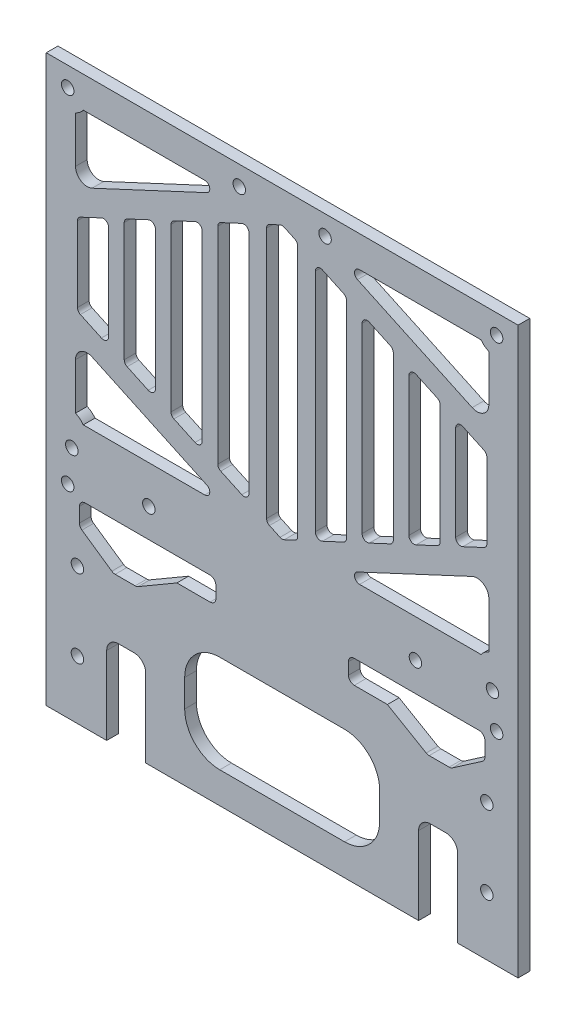
SolidWorks part; units mm, degrees
material "环氧树脂FR-4"
ref_plane "前视基准面" through (0, 0, 0) normal (0, 0, 1) x (1, 0, 0)
ref_plane "上视基准面" through (0, 0, 0) normal (0, 1, 0) x (1, 0, 0)
ref_plane "右视基准面" through (0, 0, 0) normal (1, 0, 0) x (0, 0, -1)
sketch "草图1" plane through (0, 0, 0) normal (0, 0, 1) x (1, 0, 0)
  line L1 (60.5, -72.5) -> (-60.5, -72.5)
  line L2 (60.5, -72.5) -> (60.5, 72.5)
  line L3 (60.5, 72.5) -> (-60.5, 72.5)
  line L4 (-60.5, -72.5) -> (-60.5, 72.5)
  line L5 (60.5, -72.5) -> (-60.5, 72.5) construction
  line L6 (60.5, 72.5) -> (-60.5, -72.5) construction
  point P0 (0, 0)
  dimension "D1" = 121
  dimension "D2" = 145
extrude "凸台-拉伸1" add sketch "草图1" along normal blind 3
sketch "草图2" plane through (0, 0, 3) normal (0, 0, 1) x (1, 0, 0)
  line L0 (60.5, 72.5) -> (-60.5, 72.5) construction
  line L1 (-17, -28.5) -> (-52, -28.5)
  line L2 (-17, -28.5) -> (-17, -22.5)
  line L3 (-17, -22.5) -> (-52, -22.5)
  line L4 (-52, -28.5) -> (-52, -22.5)
  line L5 (-17, -28.5) -> (-52, -22.5) construction
  line L6 (-17, -22.5) -> (-52, -28.5) construction
  line L7 (-60.5, 72.5) -> (-60.5, -72.5) construction
  line L8 (-52, -28.5) -> (-43.3, -34.5)
  line L9 (-43.3, -34.5) -> (-37.3, -34.5)
  line L10 (-37.3, -34.5) -> (-27, -28.5)
  point P0 (-34.5, -25.5)
  dimension "D1" = 98
  dimension "D2" = 6
  dimension "D3" = 35
  dimension "D4" = 26
  dimension "D5" = 8.7
  dimension "D6" = 6
  dimension "D7" = 6
  dimension "D8" = 10
extrude "切除-拉伸1" cut sketch "草图2" against normal through all contours L9 L10 L1 L8 | L4 L1 L2 L3 region at (-34.5, -25.5, 3) region at (-39.8183, -30.8871, 3)
fillet "圆角1" radius 1.5 6 edges at (-17, -28.5, 1.5) (-17, -22.5, 1.5) (-52, -22.5, 1.5) (-37.3, -34.5, 1.5) (-43.3, -34.5, 1.5) (-52, -28.5, 1.5)
mirror "镜向1" about plane through (0, 0, 0) normal (1, 0, 0) of "圆角1", "切除-拉伸1"
sketch "草图3" plane through (0, 0, 3) normal (0, 0, 1) x (1, 0, 0)
  line L0 (0, 0) -> (0, -72.5) construction
  line L1 (-60.5, -72.5) -> (60.5, -72.5) construction
  line L2 (60.5, 72.5) -> (-60.5, 72.5) construction
  line L3 (-60.5, 72.5) -> (-60.5, -72.5) construction
  circle A0 centre (-55, -20.5) radius 1.6
  circle A2 centre (55, -20.5) radius 1.6
  dimension "D3" = 3.2
  dimension "D1" = 93
  dimension "D2" = 5.5
extrude "切除-拉伸2" cut sketch "草图3" against normal through all
sketch "草图4" plane through (0, 0, 3) normal (0, 0, 1) x (1, 0, 0)
  line L0 (-53.94, -11.96) -> (-34.1862, -15.0887) construction
  line L1 (0, 0) -> (-60.5, 0) construction
  line L2 (-60.5, 72.5) -> (-60.5, -72.5) construction
  line L3 (0, 0) -> (0, -72.5) construction
  line L4 (-60.5, -72.5) -> (60.5, -72.5) construction
  circle A0 centre (-53.94, -11.96) radius 1.6
  circle A1 centre (-34.1862, -15.0887) radius 1.6
  circle A2 centre (-55, -20.5) radius 1.6 construction
  circle A3 centre (34.1862, -15.0887) radius 1.6
  circle A4 centre (53.94, -11.96) radius 1.6
  dimension "D2" = 1.06
  dimension "D4" = 3.2
  dimension "D1" = 8.54
  dimension "D3" = 9
  dimension "D5" = 20
extrude "切除-拉伸3" cut sketch "草图4" against normal through all
sketch "草图5" plane through (0, 0, 0) normal (0, 0, -1) x (-1, 0, 0)
  line L0 (52.5, -37.5) -> (52.5, -57.5) construction
  line L1 (60.5, 72.5) -> (60.5, -72.5) construction
  line L2 (60.5, -72.5) -> (-60.5, -72.5) construction
  line L3 (0, 0) -> (0, -72.5) construction
  circle A0 centre (52.5, -57.5) radius 1.6
  circle A1 centre (52.5, -37.5) radius 1.6
  circle A2 centre (-52.5, -57.5) radius 1.6
  circle A3 centre (-52.5, -37.5) radius 1.6
  dimension "D2" = 3.2
  dimension "D4" = 15
  dimension "D1" = 20
  dimension "D3" = 8
extrude "切除-拉伸4" cut sketch "草图5" against normal through all
sketch "草图6" plane through (0, 0, 3) normal (0, 0, 1) x (1, 0, 0)
  line L0 (0, 0) -> (0, 72.5) construction
  line L1 (60.5, 72.5) -> (-60.5, 72.5) construction
  line L2 (-60.5, 72.5) -> (-60.5, -72.5) construction
  circle A0 centre (-55, 67.5) radius 1.6
  circle A1 centre (55, 67.5) radius 1.6
  dimension "D1" = 5
  dimension "D3" = 3.2
  dimension "D2" = 5.5
extrude "切除-拉伸5" cut sketch "草图6" against normal through all
sketch "草图7" plane through (0, 0, 3) normal (0, 0, 1) x (1, 0, 0)
  line L7 (-8.5, 60.5364) -> (-8.5, -1.4313)
  line L8 (-8.5, -1.4313) -> (-16.5, 2.2992)
  line L10 (60.5, 72.5) -> (-60.5, 72.5) construction
  line L11 (0, 64.5) -> (-53.5, 39.5525) construction
  line L12 (-53.5, 39.5525) -> (-53.5, 19.5525) construction
  line L13 (0, 64.5) -> (0, 0) construction
  line L14 (-53.5, 29.5525) -> (53.5, 29.5525) construction
  line L15 (0, -5.3949) -> (-53.5, 19.5525) construction
  line L16 (-60.5, 72.5) -> (-60.5, -72.5) construction
  line L17 (-53.94, -11.96) -> (-34.1862, -15.0887) construction
  line L18 (0, 64.5) -> (-4, 62.6348)
  line L19 (-4, 62.6348) -> (-4, -3.5297)
  line L20 (-4, -3.5297) -> (0, -5.3949)
  line L21 (0, -5.3949) -> (0, 64.5) construction
  line L22 (-16.5, 2.2992) -> (-16.5, 56.8059)
  line L23 (-16.5, 56.8059) -> (-8.5, 60.5364)
  line L24 (-20.5, 54.9407) -> (-28.5, 51.2102)
  line L25 (-28.5, 51.2102) -> (-28.5, 7.8948)
  line L26 (-28.5, 7.8948) -> (-20.5, 4.1644)
  line L27 (-20.5, 4.1644) -> (-20.5, 54.9407)
  line L28 (-32.5, 49.345) -> (-32.5, 9.7601)
  line L29 (-32.5, 9.7601) -> (-40.5, 13.4905)
  line L30 (-40.5, 13.4905) -> (-40.5, 45.6145)
  line L31 (-40.5, 45.6145) -> (-32.5, 49.345)
  line L32 (-44.5, 43.7493) -> (-44.5, 15.3558)
  line L33 (-44.5, 15.3558) -> (-52.5, 19.0862)
  line L34 (-52.5, 19.0862) -> (-52.5, 40.0188)
  line L35 (-52.5, 40.0188) -> (-44.5, 43.7493)
  line L36 (53.94, -11.96) -> (34.1862, -15.0887) construction
  line L37 (0, -5.3949) -> (53.5, 19.5525) construction
  line L38 (53.5, 39.5525) -> (53.5, 19.5525) construction
  line L39 (0, 64.5) -> (53.5, 39.5525) construction
  line L40 (52.5, 40.0188) -> (44.5, 43.7493)
  line L41 (52.5, 19.0862) -> (52.5, 40.0188)
  line L42 (44.5, 15.3558) -> (52.5, 19.0862)
  line L43 (44.5, 43.7493) -> (44.5, 15.3558)
  line L44 (40.5, 45.6145) -> (32.5, 49.345)
  line L45 (40.5, 13.4905) -> (40.5, 45.6145)
  line L46 (32.5, 9.7601) -> (40.5, 13.4905)
  line L47 (32.5, 49.345) -> (32.5, 9.7601)
  line L48 (20.5, 4.1644) -> (20.5, 54.9407)
  line L49 (28.5, 7.8948) -> (20.5, 4.1644)
  line L50 (28.5, 51.2102) -> (28.5, 7.8948)
  line L51 (20.5, 54.9407) -> (28.5, 51.2102)
  line L52 (16.5, 56.8059) -> (8.5, 60.5364)
  line L53 (16.5, 2.2992) -> (16.5, 56.8059)
  line L54 (4, -3.5297) -> (0, -5.3949)
  line L55 (4, 62.6348) -> (4, -3.5297)
  line L56 (0, 64.5) -> (4, 62.6348)
  line L57 (8.5, -1.4313) -> (16.5, 2.2992)
  line L58 (8.5, 60.5364) -> (8.5, -1.4313)
  point P0 (0, 64.5)
  point P39 (0, 29.5525)
  dimension "D1" = 8
  dimension "D2" = 7
  dimension "D3" = 20
  dimension "D4" = 25
  dimension "D5" = 4
  dimension "D6" = 4.5
  dimension "D7" = 8
  dimension "D8" = 8
  dimension "D9" = 4
  dimension "D10" = 4
  dimension "D11" = 8
  dimension "D12" = 8
  dimension "D13" = 4
extrude "切除-拉伸6" cut sketch "草图7" against normal through all contours L35 L32 L33 L34 | L31 L28 L29 L30 | L27 L24 L25 L26 | L23 L7 L8 L22 | L54 L20 L19 L18 L56 L55 | L52 L58 L57 L53 | L48 L51 L50 L49 | L44 L47 L46 L45 | L40 L43 L42 L41
fillet "圆角2" radius 1.3 38 edges at (44.5, 43.7493, 1.5) (32.5, 49.345, 1.5) (20.5, 54.9407, 1.5) (8.5, 60.5364, 1.5) (-4, 62.6348, 1.5) (44.5, 15.3558, 1.5) (32.5, 9.7601, 1.5) (20.5, 4.1644, 1.5) (8.5, -1.4313, 1.5) (-4, -3.5297, 1.5) (-16.5, 2.2992, 1.5) (-28.5, 7.8948, 1.5) (-40.5, 13.4905, 1.5) (52.5, 40.0188, 1.5) (40.5, 45.6145, 1.5) (28.5, 51.2102, 1.5) (16.5, 56.8059, 1.5) (4, 62.6348, 1.5) (52.5, 19.0862, 1.5) (40.5, 13.4905, 1.5) (28.5, 7.8948, 1.5) (16.5, 2.2992, 1.5) (4, -3.5297, 1.5) (0, -5.3949, 1.5) (-8.5, -1.4313, 1.5) (-20.5, 4.1644, 1.5) (-32.5, 9.7601, 1.5) (-44.5, 15.3558, 1.5) (-52.5, 19.0862, 1.5) (-28.5, 51.2102, 1.5) (-52.5, 40.0188, 1.5) (-44.5, 43.7493, 1.5) (-20.5, 54.9407, 1.5) (-32.5, 49.345, 1.5) (-40.5, 45.6145, 1.5) (-16.5, 56.8059, 1.5) (-8.5, 60.5364, 1.5) (0, 64.5, 1.5)
sketch "草图8" plane through (0, 0, 0) normal (0, 0, -1) x (-1, 0, 0)
  line L0 (-53, 46.314) -> (-14, 64.5)
  line L1 (-14, 64.5) -> (-51, 64.5)
  line L2 (-53, 46.314) -> (-53, 62.9174)
  line L3 (-60.5, -72.5) -> (-60.5, 72.5) construction
  line L5 (-60.5, 72.5) -> (60.5, 72.5) construction
  line L7 (0, 72.5) -> (0, 0) construction
  line L8 (52.5, 29.5525) -> (-52.5, 29.5525) construction
  line L9 (52.5, 19.9144) -> (52.5, 39.1907) construction
  line L10 (-52.5, 19.9144) -> (-52.5, 39.1907) construction
  line L11 (53, 46.314) -> (53, 62.9174)
  line L12 (53, 46.314) -> (14, 64.5)
  line L13 (14, 64.5) -> (51, 64.5)
  line L14 (53, 12.7911) -> (14, -5.3949)
  line L15 (14, -5.3949) -> (51, -5.3949)
  line L16 (53, 12.7911) -> (53, -3.8123)
  line L17 (-53, 12.7911) -> (-53, -3.8123)
  line L18 (-53, 12.7911) -> (-14, -5.3949)
  line L19 (-14, -5.3949) -> (-51, -5.3949)
  arc A0 (-53, 62.9174) -> (-51, 64.5) centre (-55, 67.5) ccw
  arc A1 (53, 62.9174) -> (51, 64.5) centre (55, 67.5) cw
  arc A2 (53, -3.8123) -> (51, -5.3949) centre (55, -8.3949) ccw
  arc A3 (-53, -3.8123) -> (-51, -5.3949) centre (-55, -8.3949) cw
  dimension "D1" = 10
  dimension "D2" = 155
  dimension "D3" = 8
  dimension "D4" = 7.5
  dimension "D5" = 37
extrude "切除-拉伸7" cut sketch "草图8" against normal through all
fillet "圆角3" radius 1.3 4 edges at (14, -5.3949, 1.5) (-14, -5.3949, 1.5) (-14, 64.5, 1.5) (14, 64.5, 1.5)
fillet "圆角4" radius 3 4 edges at (-53, 46.314, 1.5) (-53, 12.7911, 1.5) (53, 12.7911, 1.5) (53, 46.314, 1.5)
sketch "草图10" plane through (0, 0, 0) normal (0, 0, -1) x (-1, 0, 0)
  line L0 (-45, -72.5) -> (-45, -49.5)
  line L1 (60.5, -72.5) -> (-60.5, -72.5) construction
  line L2 (-45, -49.5) -> (-35, -49.5)
  line L3 (-35, -49.5) -> (-35, -72.5)
  line L4 (-45, -72.5) -> (-35, -72.5)
  line L5 (0, 0) -> (0, -72.5) construction
  line L6 (-60.5, -72.5) -> (-60.5, 72.5) construction
  line L7 (45, -72.5) -> (45, -49.5)
  line L8 (45, -49.5) -> (35, -49.5)
  line L9 (35, -49.5) -> (35, -72.5)
  line L10 (45, -72.5) -> (35, -72.5)
  dimension "D1" = 15.5
  dimension "D2" = 10
  dimension "D3" = 23
extrude "切除-拉伸8" cut sketch "草图10" against normal through all
fillet "圆角5" radius 3 4 edges at (-45, -49.5, 1.5) (-35, -49.5, 1.5) (35, -49.5, 1.5) (45, -49.5, 1.5)
sketch "草图11" plane through (0, 0, 0) normal (0, 0, -1) x (-1, 0, 0)
  line L0 (0, 0) -> (0, -72.5) construction
  line L1 (35, -72.5) -> (-35, -72.5) construction
  line L3 (25, -64.5) -> (-25, -64.5)
  line L4 (25, -64.5) -> (25, -39.5)
  line L5 (25, -39.5) -> (-25, -39.5)
  line L6 (-25, -64.5) -> (-25, -39.5)
  line L7 (25, -64.5) -> (-25, -39.5) construction
  line L8 (25, -39.5) -> (-25, -64.5) construction
  point P5 (0, -52)
  dimension "D1" = 8
  dimension "D2" = 50
  dimension "D3" = 25
extrude "切除-拉伸9" cut sketch "草图11" against normal through all
fillet "圆角6" radius 9 4 edges at (-25, -64.5, 1.5) (25, -64.5, 1.5) (-25, -39.5, 1.5) (25, -39.5, 1.5)
sketch "草图12" plane through (0, 0, 0) normal (0, 0, -1) x (-1, 0, 0)
  line L0 (0, 64.3656) -> (0, 72.5) construction
  line L1 (-60.5, 72.5) -> (60.5, 72.5) construction
  line L2 (-55, 67.5) -> (-11, 67.5) construction
  circle A0 centre (-11, 67.5) radius 1.6
  arc A1 (0.5494, 64.2438) -> (-0.5494, 64.2438) centre (0, 63.0656) ccw construction
  circle A2 centre (11, 67.5) radius 1.6
  dimension "D1" = 3.2
  dimension "D2" = 11
extrude "切除-拉伸10" cut sketch "草图12" against normal through all
